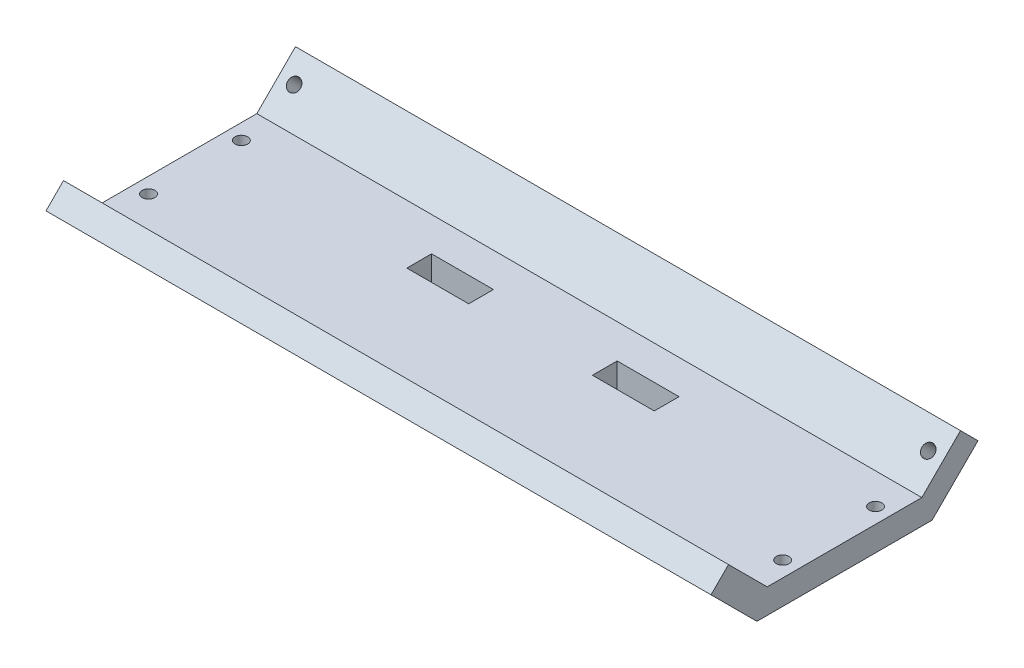
SolidWorks part; units mm, degrees
material "ABS"
ref_plane "Front Plane" through (0, 0, 0) normal (0, 0, 1) x (1, 0, 0)
ref_plane "Top Plane" through (0, 0, 0) normal (0, 1, 0) x (1, 0, 0)
ref_plane "Right Plane" through (0, 0, 0) normal (1, 0, 0) x (0, 0, -1)
sketch "Sketch2" plane through (0, 0, 0) normal (1, 0, 0) x (0, 0, -1)
  line L0 (-25, 0) -> (25, 0)
  line L1 (25, 0) -> (37.5, 12.5)
  line L2 (-25, 0) -> (-37.5, 12.5)
  line L8 (28.3137, -8) -> (43.1569, 6.8431)
  line L9 (-28.3137, -8) -> (28.3137, -8)
  line L10 (-28.3137, -8) -> (-43.1569, 6.8431)
  line L11 (-37.5, 12.5) -> (-43.1569, 6.8431)
  line L12 (37.5, 12.5) -> (43.1569, 6.8431)
  line L13 (-37.5, 12.5) -> (-50, 25) construction
  line L14 (37.5, 12.5) -> (50, 25) construction
  point P4 (0, 0)
  dimension "D2" = 135
  dimension "D3" = 135
  dimension "D1" = 100
  dimension "D4" = 25
  dimension "D5" = 8
extrude "Main" add sketch "Sketch2" along normal mid plane 215
hole_wizard "Ø4.0mm Dowel Hole2" positions "3DSketch2" profile "Sketch4" hole size "Ø4.0" standard "ANSI Metric" end condition through all
sketch3d "3DSketch2"
  line L2 (107.5, 0, -25) -> (-107.5, 0, -25) construction
  line L3 (-102.5, 0, -25) -> (-102.5, 0, -15) construction
  line L4 (-102.5, 0, -15) -> (-102.5, 0, 15) construction
  line L5 (-102.5, 0, 15) -> (-102.5, 0, 25) construction
  line L6 (107.5, 0, 25) -> (-107.5, 0, 25) construction
  line L11 (102.5, 0, -25) -> (102.5, 0, -15) construction
  line L12 (102.5, 0, -15) -> (102.5, 0, 15) construction
  line L13 (102.5, 0, 15) -> (102.5, 0, 25) construction
  line L27 (102.5, 0, -25) -> (102.5, 7.0711, -32.0711) construction
  line L29 (102.5, 0, 25) -> (102.5, 7.0711, 32.0711) construction
  line L31 (-102.5, 7.0711, 32.0711) -> (-102.5, 0, 25) construction
  line L35 (-102.5, 7.0711, -32.0711) -> (-107.5, 7.0711, -32.0711) construction
  line L36 (-107.5, 12.5, -37.5) -> (-107.5, 0, -25) construction
  line L38 (-102.5, 7.0711, 32.0711) -> (-107.5, 7.0711, 32.0711) construction
  line L39 (-107.5, 0, 25) -> (-107.5, 12.5, 37.5) construction
  line L41 (102.5, 7.0711, -32.0711) -> (107.5, 7.0711, -32.0711) construction
  line L42 (107.5, 12.5, -37.5) -> (107.5, 0, -25) construction
  line L44 (102.5, 7.0711, 32.0711) -> (107.5, 7.0711, 32.0711) construction
  line L45 (107.5, 0, 25) -> (107.5, 12.5, 37.5) construction
  line L47 (102.5, 0, 25) -> (107.5, 0, 25) construction
  line L49 (-102.5, 0, 25) -> (-107.5, 0, 25) construction
  line L51 (-102.5, 7.0711, -32.0711) -> (-102.5, 0, -25) construction
  point P0 (-102.5, 7.0711, -32.0711)
  point P2 (-102.5, 0, -15)
  point P4 (-102.5, 0, 15)
  point P6 (-102.5, 7.0711, 32.0711)
  point P8 (102.5, 7.0711, 32.0711)
  point P10 (102.5, 0, 15)
  point P12 (102.5, 0, -15)
  point P14 (102.5, 7.0711, -32.0711)
  dimension "D1" = 5
  dimension "D2" = 10
  dimension "D3" = 10
sketch "Sketch4" plane through (-102.5, 7.0711, -32.0711) normal (1, 0, 0) x (0, -0.7071, 0.7071)
  line L0 (0, 0) -> (0, 18.4957)
  line L1 (0, 18.4957) -> (2.05, 18.4957)
  line L2 (2.05, 18.4957) -> (2.05, 0)
  line L5 (2.05, 0) -> (0, 0)
  line L11 (0, -6.35) -> (0, 107.95) construction
  dimension "Thru Hole Dia." = 4.1
  dimension "Thru Hole Depth" = 18.4957
sketch "Sketch5" plane through (0, 0, 0) normal (0, 1, 0) x (1, 0, 0)
  line L0 (0, 0) -> (-50, 0) construction
  line L1 (-73.25, 11.775) -> (-26.75, 11.775) construction
  line L2 (-73.25, 11.775) -> (-73.25, -11.775) construction
  line L3 (-73.25, -11.775) -> (-26.75, -11.775) construction
  line L4 (-26.75, 11.775) -> (-26.75, -11.775) construction
  line L5 (-73.25, 11.775) -> (-26.75, -11.775) construction
  line L6 (-73.25, -11.775) -> (-26.75, 11.775) construction
  circle A0 centre (-73.25, 11.775) radius 4
  circle A1 centre (-26.75, 11.775) radius 4
  circle A2 centre (-26.75, -11.775) radius 4
  circle A3 centre (-73.25, -11.775) radius 4
  circle A4 centre (-73.25, 11.775) radius 2.05
  circle A5 centre (-26.75, 11.775) radius 2.05
  circle A6 centre (-26.75, -11.775) radius 2.05
  circle A7 centre (-73.25, -11.775) radius 2.05
  point P0 (-50, 0)
  dimension "D1" = 8
  dimension "D2" = 4.1
  dimension "D3" = 46.5
  dimension "D4" = 23.55
  dimension "D5" = 50
extrude "ESP32 pegs" [suppressed] add sketch "Sketch5" along normal blind 5.7
sketch "Sketch6" plane through (0, 0, 0) normal (0, 1, 0) x (1, 0, 0)
  line L0 (0, 0) -> (0, 10) construction
  line L1 (20, 14) -> (40, 14)
  line L2 (20, 14) -> (20, 6)
  line L3 (20, 6) -> (40, 6)
  line L4 (40, 14) -> (40, 6)
  line L5 (20, 14) -> (40, 6) construction
  line L6 (20, 6) -> (40, 14) construction
  line L7 (30, 10) -> (0, 10) construction
  line L8 (-40, 14) -> (-20, 14)
  line L9 (-40, 14) -> (-40, 6)
  line L10 (-40, 6) -> (-20, 6)
  line L11 (-20, 14) -> (-20, 6)
  line L12 (-40, 14) -> (-20, 6) construction
  line L13 (-40, 6) -> (-20, 14) construction
  line L14 (0, 10) -> (-30, 10) construction
  point P0 (30, 10)
  point P5 (-30, 10)
  dimension "D1" = 80
  dimension "D2" = 8
  dimension "D3" = 40
  dimension "D4" = 10
extrude "Shelf cut" cut sketch "Sketch6" against normal through all
equation "\"D1@Main\" = \"length\""
equation "\"D5@Sketch2\"=\"skin_th\""
equation "\"D1@Sketch2\"=\"height\""
equation "\"D2@Sketch6\"=\"skin_th\""
equation "\"length\" = 215mm"
equation "\"width\" = 220mm"
equation "\"height\" = 100mm"
equation "\"skin_th\" = 8mm"
equation "\"shelf_height\" = 10mm"
equation "\"D4@Sketch6\"=\"shelf_height\""
